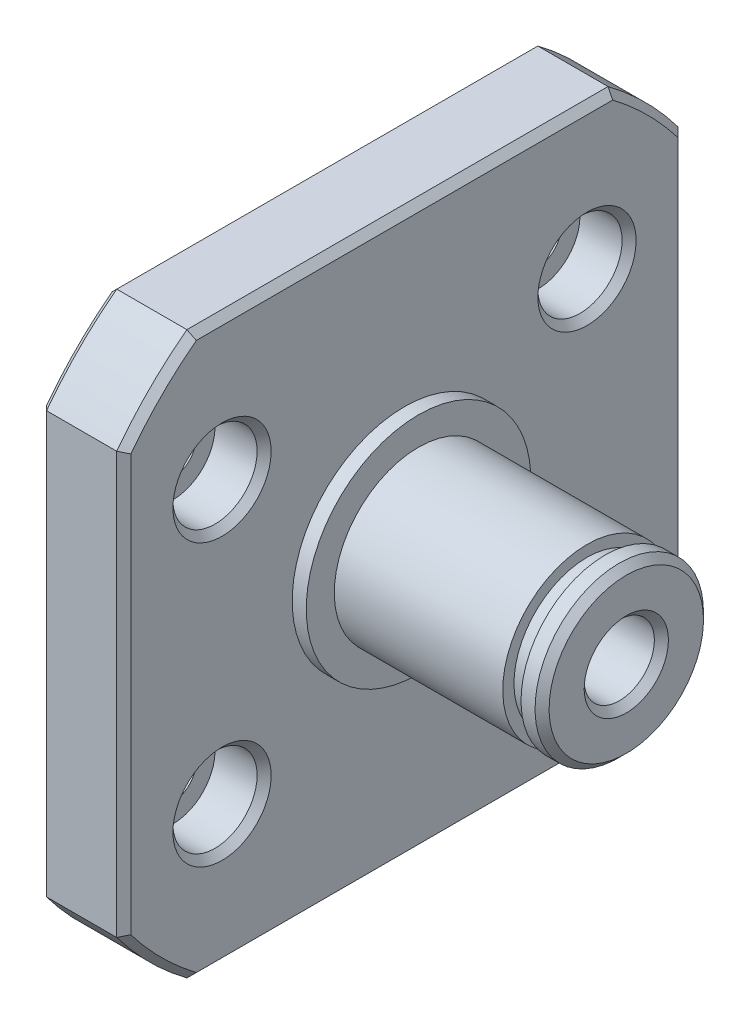
SolidWorks part; units mm, degrees
material "6061-T6 (GB)"
ref_plane "前视" through (0, 0, 0) normal (0, 0, 1) x (1, 0, 0)
ref_plane "上视" through (0, 0, 0) normal (0, 1, 0) x (1, 0, 0)
ref_plane "右视" through (0, 0, 0) normal (1, 0, 0) x (0, 0, -1)
sketch "草图1" plane through (0, 0, 0) normal (0, 0, 1) x (1, 0, 0)
  line L0 (0, 1.5) -> (0, 25)
  line L5 (0, 25) -> (6, 25)
  line L6 (6, 25) -> (6, 8)
  line L7 (6, 8) -> (7, 8)
  line L8 (7, 8) -> (7, 6)
  line L9 (7, 6) -> (19, 6)
  line L10 (19, 6) -> (19, 5.2)
  line L11 (19, 5.2) -> (20.3, 5.2)
  line L12 (20.3, 5.2) -> (20.3, 6)
  line L13 (20.3, 6) -> (21.8, 6)
  line L14 (21.8, 6) -> (21.8, 2.5)
  line L15 (21.8, 2.5) -> (16.8, 2.5)
  line L16 (16.8, 2.5) -> (16.8, 1.5)
  line L17 (16.8, 1.5) -> (0, 1.5)
  line L18 (15.7758, 0) -> (0, 0) construction
  dimension "D1" = 3
  dimension "D2" = 5
  dimension "D4" = 0.8
  dimension "D5" = 1.5
  dimension "D6" = 12
  dimension "D7" = 1
  dimension "D8" = 12
  dimension "D9" = 16
  dimension "D3" = 1.3
  dimension "D11" = 6
  dimension "D10" = 50
  dimension "D12" = 5
revolve "旋转1" add sketch "草图1" angle 360 about L18
sketch "草图5" plane through (6, 0, 0) normal (1, 0, 0) x (0, 0, -1)
  line L0 (0, 0) -> (0, 26.3998) construction
  line L1 (0, 0) -> (-35.521, 0) construction
  line L3 (-15, 20) -> (15, 20)
  line L4 (-20, 15) -> (-20, -15)
  line L5 (-15, -20) -> (15, -20)
  line L6 (20, 15) -> (20, -15)
  circle A0 centre (-13, 10) radius 1.65
  circle A1 centre (-13, -10) radius 1.65
  circle A2 centre (13, -10) radius 1.65
  circle A3 centre (13, 10) radius 1.65
  circle A4 centre (0, 0) radius 25 construction
  arc A5 (-20, 15) -> (-20, -15) centre (0, 0) ccw
  arc A6 (15, 20) -> (-15, 20) centre (0, 0) ccw
  arc A7 (20, -15) -> (20, 15) centre (0, 0) ccw
  arc A8 (-15, -20) -> (15, -20) centre (0, 0) ccw
  dimension "D3" = 20
  dimension "D4" = 26
  dimension "D5" = 3.3
  dimension "D1" = 40
  dimension "D2" = 40
extrude "切除-拉伸6" cut sketch "草图5" against normal through all
sketch "草图6" plane through (6, 0, 0) normal (1, 0, 0) x (0, 0, -1)
  circle A0 centre (-13, 10) radius 3
  circle A1 centre (13, 10) radius 3
  circle A2 centre (-13, -10) radius 3
  circle A3 centre (13, -10) radius 3
  dimension "D1" = 6
extrude "切除-拉伸7" cut sketch "草图6" against normal blind 3.5
chamfer "倒角2" distance 0.5 angle 45 27 edges at (0, 1.5, 0) (21.8, 6, 0) (21.8, 2.5, 0) (6, 17.6777, 17.6777) (6, 20, 0) (6, 17.6777, -17.6777) (6, 0, -20) (6, -17.6777, -17.6777) (6, -20, 0) (6, -17.6777, 17.6777) (6, 0, 20) (0, -8.35, -13) (0, -11.65, 13) (0, 11.65, 13) (0, 8.35, -13) (0, 17.6777, -17.6777) (0, 20, 0) (0, 17.6777, 17.6777) (0, 0, 20) (0, -17.6777, 17.6777) (0, -20, 0) (0, -17.6777, -17.6777) (0, 0, -20) (6, -7, -13) (6, -7, 13) (6, 13, -13) (6, 13, 13)
sketch "草图7" plane through (21.8, 0, 0) normal (1, 0, 0) x (0, 0, -1)
  line L0 (-10.9669, 0) -> (12.0581, 0) construction
  line L1 (-6.0597, 0) -> (6.0597, 0) construction
  line L2 (-2, 1.5) -> (2, 1.5)
  line L3 (-2, -1.5) -> (2, -1.5)
  circle A6 centre (0, 0) radius 2.5 construction
  arc A7 (2, -1.5) -> (2, 1.5) centre (0, 0) ccw
  arc A8 (-2, 1.5) -> (-2, -1.5) centre (0, 0) ccw
  point P6 (0, 0)
  dimension "D1" = 3
extrude "切除-拉伸8" cut sketch "草图7" against normal through all
